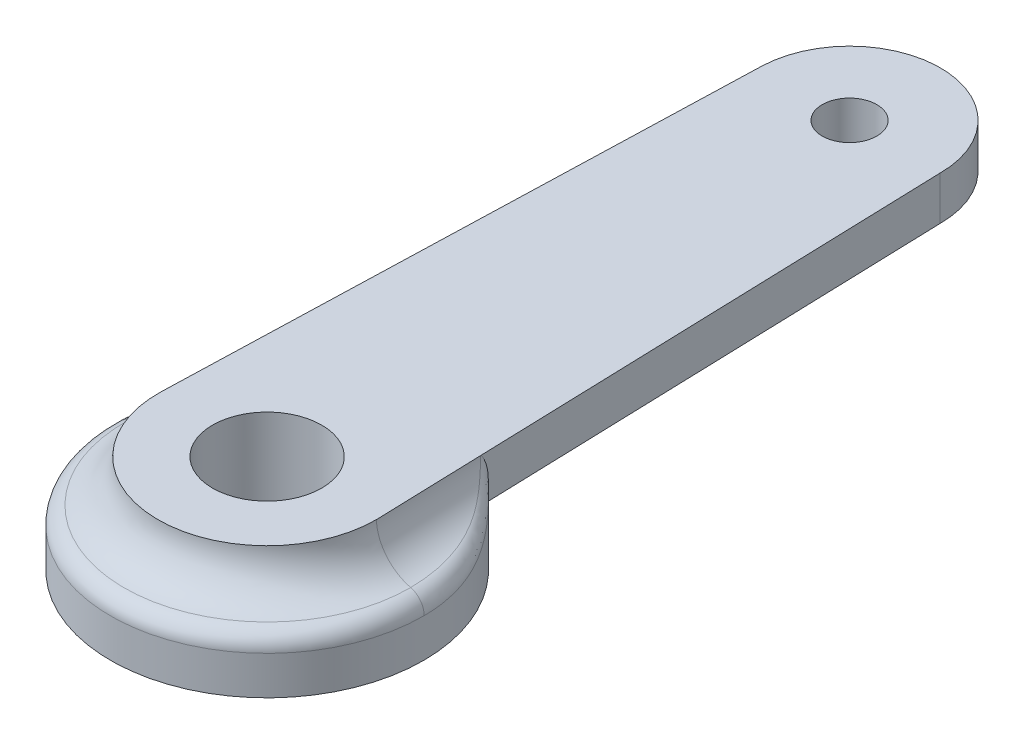
SolidWorks part; units mm, degrees
ref_plane "Front Plane" through (0, 0, 0) normal (0, 0, 1) x (1, 0, 0)
ref_plane "Top Plane" through (0, 0, 0) normal (0, 1, 0) x (1, 0, 0)
ref_plane "Right Plane" through (0, 0, 0) normal (1, 0, 0) x (0, 0, -1)
sketch "Sketch1" plane through (0, 0, 0) normal (0, 1, 0) x (1, 0, 0)
  line L0 (3, 0) -> (2.4974, 15.9842)
  line L2 (-2.4962, 16.0784) -> (-2.9985, 0.0942)
  line L3 (0, 16) -> (0, 0) construction
  arc A0 (-2.9985, 0.0942) -> (2.9941, 0.1885) centre (0, 0) ccw
  circle A1 centre (0, 0) radius 1.5
  arc A2 (-2.4962, 16.0784) -> (2.4974, 15.9842) centre (0, 16) cw
  circle A3 centre (0, 16) radius 0.75
  dimension "D1" = 3
  dimension "D2" = 1.5
  dimension "D4" = 1.5
  dimension "D3" = 1.8
  dimension "D5" = 16
extrude "Boss-Extrude1" add sketch "Sketch1" along normal blind 1.2 contours A2 L2 A0 L0 A3 A1 region at (-0.0007, 0, -7.7926)
sketch "Sketch2" plane through (0, 0, 0) normal (0, -1, 0) x (1, 0, 0)
  circle A0 centre (0, 0) radius 4.3
  circle A1 centre (0, 0) radius 1.5
extrude "Boss-Extrude2" add sketch "Sketch2" along normal blind 1.5
fillet "Fillet1" radius 1.25 3 edges at (-2.9501, 0, -1.6338) (2.9501, 0, -1.5874) (-0.0471, 0, 2.9996)
fillet "Fillet2" radius 0.5 2 edges at (3.3107, 0.3356, -2.744) (-3.2019, 0.4477, -2.8702)
